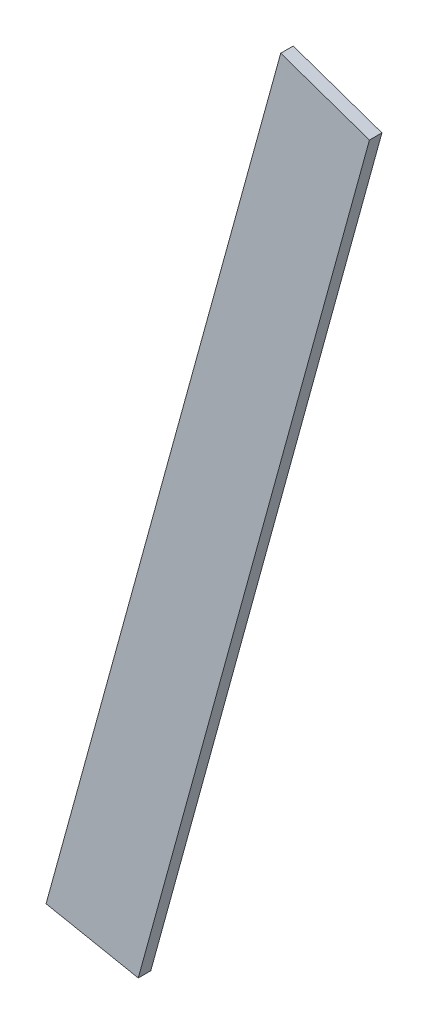
SolidWorks part; units mm, degrees
ref_plane "Front Plane" through (0, 0, 0) normal (0, 0, 1) x (1, 0, 0)
ref_plane "Top Plane" through (0, 0, 0) normal (0, 1, 0) x (1, 0, 0)
ref_plane "Right Plane" through (0, 0, 0) normal (1, 0, 0) x (0, 0, -1)
sketch "Sketch1" plane through (0, 0, 0) normal (0, 0, 1) x (1, 0, 0)
  line L0 (31.9853, -10.9167) -> (17.2294, -8.0051)
  line L2 (17.2294, -8.0051) -> (54.7831, 128.6574)
  line L4 (31.9853, -10.9167) -> (68.9831, 123.7229)
  line L5 (68.9831, 123.7229) -> (54.7831, 128.6574)
  line L6 (133.2391, 101.3941) -> (-55.6796, 167.0428) construction
  line L7 (-97.0067, 14.536) -> (99.2099, -24.1814) construction
  dimension "D1" = 15
extrude "Boss-Extrude1" add sketch "Sketch1" along normal blind 2
ref_plane "Plane1" through (25.297, -6.9514, 0) normal (0.9643, -0.265, 0) x (0, 0, -1)
